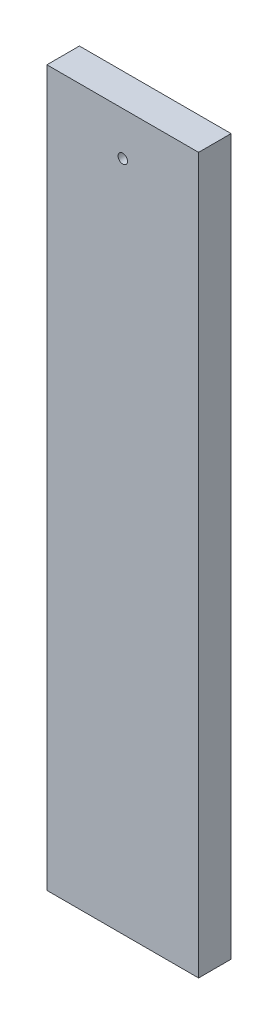
SolidWorks part; units mm, degrees
ref_plane "Front Plane" through (0, 0, 0) normal (0, 0, 1) x (1, 0, 0)
ref_plane "Top Plane" through (0, 0, 0) normal (0, 1, 0) x (1, 0, 0)
ref_plane "Right Plane" through (0, 0, 0) normal (1, 0, 0) x (0, 0, -1)
sketch "Sketch1" plane through (0, 0, 0) normal (0, 1, 0) x (1, 0, 0)
  line L1 (0, 0) -> (88.9, 0)
  line L2 (0, 0) -> (0, 19.05)
  line L3 (0, 19.05) -> (88.9, 19.05)
  line L4 (88.9, 0) -> (88.9, 19.05)
  dimension "D1" = 19.05
  dimension "D2" = 88.9
extrude "Boss-Extrude1" add sketch "Sketch1" along normal blind 419.1
sketch "Sketch2" plane through (0, 0, 0) normal (0, 0, 1) x (1, 0, 0)
  line L0 (44.45, 419.1) -> (44.45, 393.7) construction
  line L1 (0, 419.1) -> (88.9, 419.1) construction
  circle A0 centre (44.45, 393.7) radius 2.7781
  dimension "D1" = 5.5562
  dimension "D2" = 25.4
extrude "Cut-Extrude1" cut sketch "Sketch2" against normal through all
